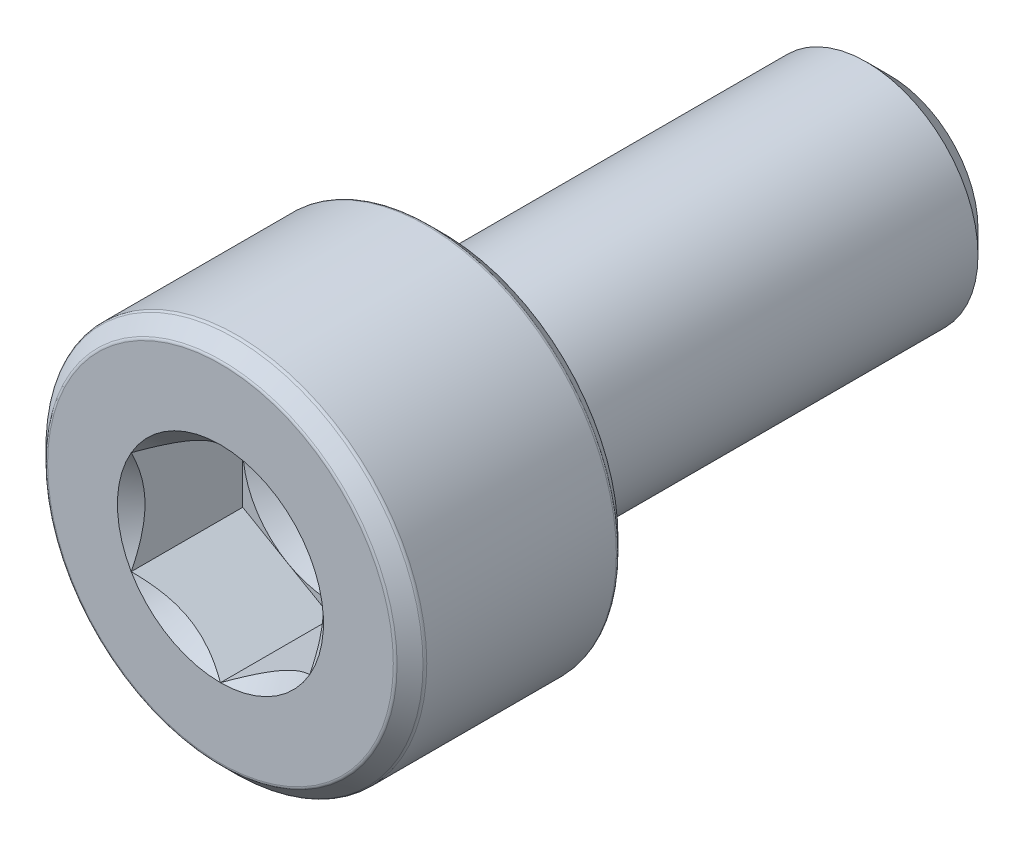
SolidWorks part; units mm, degrees
ref_plane "Front Plane" through (0, 0, 0) normal (0, 0, 1) x (1, 0, 0)
ref_plane "Top Plane" through (0, 0, 0) normal (0, 1, 0) x (1, 0, 0)
ref_plane "Right Plane" through (0, 0, 0) normal (1, 0, 0) x (0, 0, -1)
sketch "Sketch1" plane through (0, 0, 0) normal (1, 0, 0) x (0, 0, -1)
  line L0 (-7.5, 0) -> (7.5, 0) construction
  line L1 (-7.5, 0) -> (-7.5, 4.25)
  line L2 (-7.5, 4.25) -> (-2.5, 4.25)
  line L3 (-2.5, 4.25) -> (-2.5, 2.5)
  line L4 (-2.5, 2.5) -> (6.9804, 2.5)
  line L5 (7.45, 2.5866) -> (7.85, 1.8938) construction
  line L6 (7.85, 1.8938) -> (8.25, 2.5866) construction
  line L7 (8.25, 2.5866) -> (7.45, 2.5866) construction
  line L8 (6.9804, 2.5) -> (7.5, 1.9804)
  line L9 (7.5, 1.9804) -> (7.5, 0)
  line L10 (7.5, 2.5) -> (8.2, 2.5) construction
  line L11 (7.85, 2.5866) -> (7.85, 2.5) construction
  line L12 (7.85, 2.5) -> (7.85, 1.9804) construction
  line L13 (7.85, 1.9804) -> (7.85, 1.8938) construction
  line L14 (7.8, 1.9804) -> (7.9, 1.9804)
  line L15 (7.475, 2.5433) -> (8.225, 2.5433)
  line L16 (7.9, 1.9804) -> (8.225, 2.5433)
  line L17 (7.8, 1.9804) -> (7.475, 2.5433)
  line L18 (-7.5, 2) -> (-5, 2)
  line L19 (-5, 2) -> (-5, 0)
  line L20 (4.7, 2.5) -> (4.7, -2.5) construction
  point P20 (7.85, 2.5433)
  point P22 (4.7, -2.5)
  point P28 (4.7, 0)
  point P29 (6.9804, -2.5)
  dimension "Head Diameter" = 8.5
  dimension "Length" = 10
  dimension "Head Height" = 5
  dimension "D2" = 5
  dimension "D1" = 45
  dimension "Thread Pitch" = 0.8
  dimension "D3" = 0.1
  dimension "Drive Size" = 4
  dimension "D4" = 2.8
  dimension "D5" = 2.5
sketch "Sketch3" plane through (0, 0, 0) normal (1, 0, 0) x (0, 0, -1)
  line L0 (-7.5, 3.8748) -> (-7.5, 2)
  line L1 (-7.5, 2) -> (-5, 2)
  line L2 (-5, 2) -> (-5, 0)
  line L3 (-5, 0) -> (7.5, 0)
  line L4 (7.5, 0) -> (7.5, 1.9804)
  line L5 (7.5, 1.9804) -> (6.9804, 2.5)
  line L6 (6.9804, 2.5) -> (-2.5, 2.5)
  line L7 (-2.5, 2.5) -> (-2.5, 3.8748)
  line L8 (-2.8752, 4.25) -> (-7.1248, 4.25)
  line L9 (-7.4751, 3.9349) -> (-7.1849, 4.2251)
  line L10 (-2.8151, 4.2251) -> (-2.5249, 3.9349)
  line L11 (-7.5, 4.25) -> (-2.5, 4.25) construction
  arc A0 (-2.5249, 3.9349) -> (-2.5, 3.8748) centre (-2.585, 3.8748) cw
  arc A1 (-2.8151, 4.2251) -> (-2.8752, 4.25) centre (-2.8752, 4.165) ccw
  arc A2 (-7.1849, 4.2251) -> (-7.1248, 4.25) centre (-7.1248, 4.165) cw
  arc A3 (-7.4751, 3.9349) -> (-7.5, 3.8748) centre (-7.415, 3.8748) ccw
  point P29 (-7.5, 3.91)
  dimension "D3" = 0.085
  dimension "D1" = 45
  dimension "D2" = 0.34
revolve "Revolve1" add sketch "Sketch3" angle 360 about L0
sketch "Sketch4" plane through (0, 0, 7.5) normal (0, 0, 1) x (1, 0, 0)
  line L1 (0, 2.3094) -> (-2, 1.1547)
  line L2 (-2, 1.1547) -> (-2, -1.1547)
  line L3 (-2, -1.1547) -> (0, -2.3094)
  line L4 (0, -2.3094) -> (2, -1.1547)
  line L5 (2, -1.1547) -> (2, 1.1547)
  line L6 (2, 1.1547) -> (0, 2.3094)
  circle A0 centre (0, 0) radius 2 construction
extrude "Cut-Extrude1" cut sketch "Sketch4" against normal up to vertex (2.5 mm away) up to point (0, 2, 5)
sketch "Sketch5" plane through (0, 0, 7.5) normal (0, 0, 1) x (1, 0, 0)
  circle A0 centre (0, 0) radius 2.3094
extrude "Cut-Extrude2" cut sketch "Sketch5" against normal up to next (2.5 mm away) draft 45
sketch "Sketch10" plane through (0, 0, 5) normal (0, 0, 1) x (1, 0, 0)
  line L0 (2, 1.1547) -> (2, -1.1547) construction
  circle A0 centre (0, 0) radius 2
extrude "Cut-Extrude3" cut sketch "Sketch10" against normal through all draft 60
split "Split1" [suppressed] bodies to split 112
sketch "Sketch6" [suppressed] plane through (0, 0, -7.5) normal (0, 0, -1) x (-1, 0, 0)
  circle A0 centre (0, 0) radius 2.5 construction
  circle A1 centre (0, 0) radius 2.5
curve "Helix/Spiral1" [suppressed] pitch 0.8 height 10.8 turns 13.5
sketch "Sketch7" [suppressed] plane through (0, 0, 0) normal (1, 0, 0) x (0, 0, -1)
  line L0 (7.8, 1.9804) -> (7.9, 1.9804) construction
  line L1 (7.8, 1.9804) -> (7.475, 2.5433) construction
  line L2 (7.475, 2.5433) -> (8.225, 2.5433) construction
  line L3 (7.9, 1.9804) -> (8.225, 2.5433) construction
  line L4 (7.8, 1.9804) -> (7.9, 1.9804)
  line L5 (7.8, 1.9804) -> (7.475, 2.5433)
  line L6 (7.475, 2.5433) -> (8.225, 2.5433)
  line L7 (7.9, 1.9804) -> (8.225, 2.5433)
sweep "Cut-Sweep1" [suppressed] cut profiles "Sketch7" path "Helix/Spiral1"
sketch "Sketch11" [suppressed] plane through (0, 0, 0) normal (1, 0, 0) x (0, 0, -1)
  line L0 (-2.5, 2.7) -> (-2.3, 2.5) construction
  line L1 (-2.5, 4.25) -> (-2.5, 2.5) construction
  line L2 (-2.5, 2.5) -> (6.9804, 2.5) construction
  line L3 (-2.3, 2.5) -> (-1.7, 2.5)
  line L4 (-1.7, 2.5) -> (0.8, 0)
  line L5 (-7.5, 0) -> (7.5, 0) construction
  line L6 (0.8, 0) -> (-2.5, 0)
  line L7 (-2.5, 0) -> (-2.5, 2.7)
  line L8 (-2.5, -3.91) -> (-2.5, 3.91) construction
  arc A0 (-2.3, 2.5) -> (-2.5, 2.7) centre (-2.3, 2.7) cw
  dimension "D4" = 0.8
  dimension "D1" = 45
  dimension "D2" = 0.2
  dimension "D3" = 45
revolve "Revolve2" [suppressed] add sketch "Sketch11" angle 360 about L6
sketch "Sketch12" [suppressed] plane through (0, 0, 7.5) normal (0, 0, 1) x (1, 0, 0)
  line L0 (0, 0) -> (0, 4.25) construction
  line L1 (0, 0) -> (0.2125, 4.4962) construction
  line L2 (0.2125, 4.4962) -> (-0.2125, 4.4962)
  line L3 (-0.2125, 4.4962) -> (0, 0) construction
  line L4 (-0.2125, 4.4962) -> (-0.0093, 4.1229)
  line L5 (0.0093, 4.1229) -> (0.2125, 4.4962)
  line L7 (0, 3.8748) -> (0, 3.9349) construction
  circle A0 centre (0, 0) radius 4.25 construction
  arc A2 (-0.0093, 4.1229) -> (0.0093, 4.1229) centre (0, 4.128) ccw
  point P11 (0, 4.1057)
  point P13 (0, 3.9048)
  point P15 (0, 4.1173)
  dimension "D3" = 0.0106
  dimension "D1" = 0.425
  dimension "D2" = 5.412
  dimension "D4" = 0.2125
extrude "Cut-Extrude4" [suppressed] cut sketch "Sketch12" against normal up to vertex
sketch "Sketch13" [suppressed] plane through (0, 0, 5) normal (0, 0, 1) x (1, 0, 0)
  circle A0 centre (0, 0) radius 4.25
  circle A2 centre (0, 0) radius 2.5
  arc A3 (0.0781, 4.2493) -> (-0.0781, 4.2493) centre (0, 0) ccw construction
extrude "Boss-Extrude1" [suppressed] add sketch "Sketch13" along normal through all draft 45
fillet "Fillet1" [suppressed] radius 0.0125
pattern_circular "CirPattern1" [suppressed] count 98 over 360 of bodies 116
equation "\"D3@Sketch1\" = \"Thread Pitch@Sketch1\" / 8"
equation "\"D4@Sketch1\" = \"Thread Pitch@Sketch1\" * 3.5"
equation "\"D3@Helix/Spiral1\" = \"Length@Sketch1\" + \"Thread Pitch@Sketch1\""
equation "\"D4@Helix/Spiral1\" = \"Thread Pitch@Sketch1\""
equation "\"D5@Sketch1\"=\"Head Height@Sketch1\"*0.5"
equation "\"D2@Sketch3\"=\"Head Diameter@Sketch1\" /25"
equation "\"D2@Sketch11\"=\"Thread Pitch@Sketch1\" / 4"
equation "\"D1@Sketch12\"=\"Head Diameter@Sketch1\"*0.05"
equation "\"D1@CirPattern1\"=int(360/(\"D2@Sketch12\"*.675))"
equation "\"D3@Sketch12\"=\"D1@Sketch12\"*00.025"
equation "\"D4@Sketch11\"=\"Thread Pitch@Sketch1\" "
equation "\"D3@Sketch3\"=\"D2@Sketch3\"*0.25"
equation "\"D4@Sketch12\"= \"D2@Sketch3\"*0.625"
